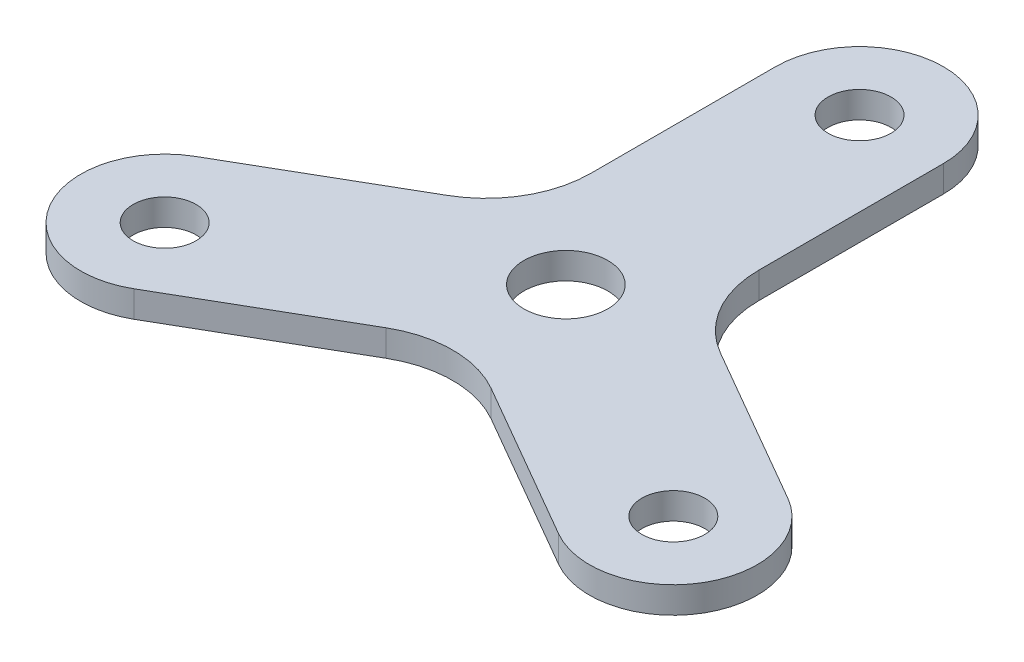
SolidWorks part; units mm, degrees
note: '?' marks a value the reader was unsure of.
ref_plane "Front Plane" through (0, 0, 0) normal (0, 0, 1) x (1, 0, 0)
ref_plane "Top Plane" through (0, 0, 0) normal (0, 1, 0) x (1, 0, 0)
ref_plane "Right Plane" through (0, 0, 0) normal (1, 0, 0) x (0, 0, -1)
other "Bounding Box"
ref_plane "Default Plane" through (13.8565, 3.175, 6.7999) normal (0, -1, 0) x (-1, 0, 0)
sketch "Sketch1" plane through (0, 0, 0) normal (0, 1, 0) x (1, 0, 0)
  line L0 (0, 0) -> (0, 17.78) construction
  line L2 (-5.08, 17.78) -> (5.08, 17.78) construction
  line L3 (-5.08, 17.78) -> (-5.08, 0)
  line L4 (-5.08, 0) -> (5.08, 0)
  line L5 (5.08, 17.78) -> (5.08, 0)
  line L6 (-5.08, 17.78) -> (5.08, 0) construction
  line L7 (-5.08, 0) -> (5.08, 17.78) construction
  circle A0 centre (0, 17.78) radius 1.905
  arc A1 (-5.08, 17.78) -> (5.08, 17.78) centre (0, 17.78) cw
  point P8 (0, 8.89)
  point P9 (10.7869, -6.0827)
  dimension "D2" = 3.81
  dimension "D3" = 5.08
  dimension "D1" = 17.78
extrude "Boss-Extrude1" add sketch "Sketch1" along normal mid plane 1.6002
ref_axis "Axis1" through (0, -0.8801, 0) along (0, 1, 0)?
pattern_circular "CirPattern1" count 3 over 360 about axis through (0, 0, 0) along (0, 1, 0) of "Boss-Extrude1"
sketch "Sketch2" plane through (0, 0.8001, 0) normal (0, 1, 0) x (1, 0, 0)
  circle A0 centre (0, 0) radius 2.54
  dimension "D1" = 5.08
extrude "Cut-Extrude1" cut sketch "Sketch2" against normal through all
fillet "Fillet1" radius 6.35 3 edges at (0, 0, 5.8659) (5.08, 0, -2.9329) (-5.08, 0, -2.9329)
